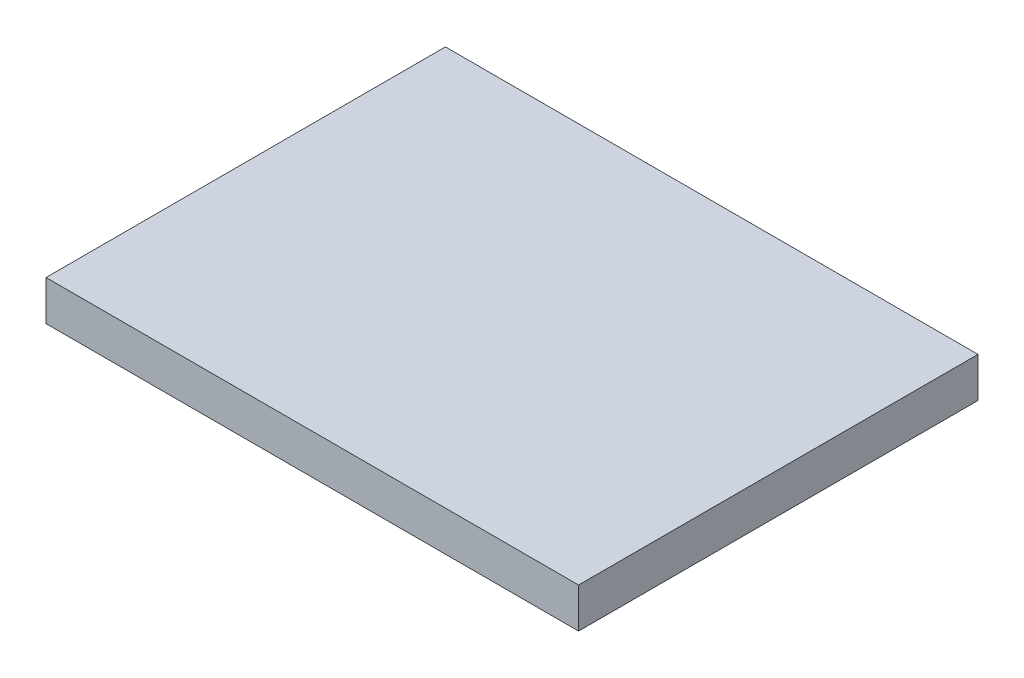
SolidWorks part; units mm, degrees
ref_plane "Front Plane" through (0, 0, 0) normal (0, 0, 1) x (1, 0, 0)
ref_plane "Top Plane" through (0, 0, 0) normal (0, 1, 0) x (1, 0, 0)
ref_plane "Right Plane" through (0, 0, 0) normal (1, 0, 0) x (0, 0, -1)
sketch "Sketch1" plane through (0, 0, 0) normal (0, 1, 0) x (1, 0, 0)
  line L1 (-10, -7.5) -> (10, -7.5)
  line L2 (-10, -7.5) -> (-10, 7.5)
  line L3 (-10, 7.5) -> (10, 7.5)
  line L4 (10, -7.5) -> (10, 7.5)
  line L5 (-10, -7.5) -> (10, 7.5) construction
  line L6 (-10, 7.5) -> (10, -7.5) construction
  point P0 (0, 0)
  dimension "D1" = 20
  dimension "D2" = 15
extrude "Boss-Extrude1" add sketch "Sketch1" along normal blind 1.5
